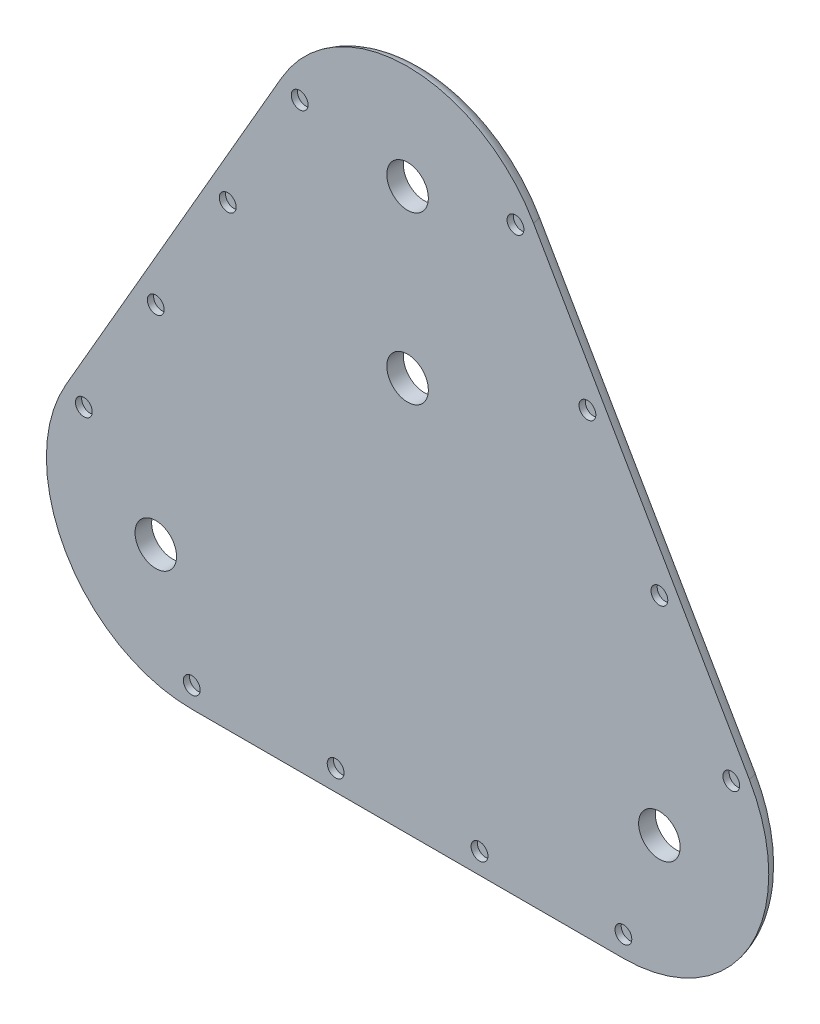
SolidWorks part; units mm, degrees
ref_plane "Plano frontal" through (0, 0, 0) normal (0, 0, 1) x (1, 0, 0)
ref_plane "Plano superior" through (0, 0, 0) normal (0, 1, 0) x (1, 0, 0)
ref_plane "Plano direito" through (0, 0, 0) normal (1, 0, 0) x (0, 0, -1)
sketch "Esboço1" plane through (0, 0, 0) normal (0, 0, 1) x (1, 0, 0)
  line L3 (-30.3109, 77.5) -> (-82.2724, -12.5)
  line L4 (-51.9615, -65) -> (51.9615, -65)
  line L5 (82.2724, -12.5) -> (30.3109, 77.5)
  arc A3 (-82.2724, -12.5) -> (-51.9615, -65) centre (-51.9615, -30) ccw
  arc A4 (51.9615, -65) -> (82.2724, -12.5) centre (51.9615, -30) ccw
  arc A5 (30.3109, 77.5) -> (-30.3109, 77.5) centre (0, 60) ccw
extrude "Ressalto-extrusão1" add sketch "Esboço1" along normal blind 4
sketch "Esboço2" plane through (0, 0, 0) normal (0, 0, 1) x (1, 0, 0)
  line L0 (0, 0) -> (0, 70) construction
  circle A3 centre (0, 70) radius 5
  circle A4 centre (60.6218, -35) radius 5
  circle A5 centre (-60.6218, -35) radius 5
  circle A6 centre (0, 30) radius 5
  point P13 (0, 0)
  dimension "D1" = 70
  dimension "D2" = 10
  dimension "D4" = 10
  dimension "D5" = 30
  dimension "D3" = 3
extrude "Corte-extrusão1" cut sketch "Esboço2" along normal up to surface (4 mm away) up to face at (0, 0, 4)
sketch "Esboço3" plane through (0, 0, 4) normal (0, 0, 1) x (1, 0, 0)
  line L0 (-25.9808, 75) -> (-77.9423, -15) construction
  line L1 (-51.9615, -60) -> (51.9615, -60) construction
  line L2 (77.9423, -15) -> (25.9808, 75) construction
  line L3 (-30.3109, 77.5) -> (-82.2724, -12.5)
  line L4 (-51.9615, -65) -> (51.9615, -65)
  line L5 (82.2724, -12.5) -> (30.3109, 77.5)
  line L6 (-30.3109, 77.5) -> (-82.2724, -12.5) construction
  line L7 (-51.9615, -65) -> (51.9615, -65) construction
  line L8 (82.2724, -12.5) -> (30.3109, 77.5) construction
  arc A0 (-77.9423, -15) -> (-51.9615, -60) centre (-51.9615, -30) ccw construction
  arc A1 (51.9615, -60) -> (77.9423, -15) centre (51.9615, -30) ccw construction
  arc A2 (25.9808, 75) -> (-25.9808, 75) centre (0, 60) ccw construction
  arc A3 (30.3109, 77.5) -> (-30.3109, 77.5) centre (0, 60) ccw
  arc A4 (-82.2724, -12.5) -> (-51.9615, -65) centre (-51.9615, -30) ccw
  arc A5 (51.9615, -65) -> (82.2724, -12.5) centre (51.9615, -30) ccw
  arc A6 (30.3109, 77.5) -> (-30.3109, 77.5) centre (0, 60) ccw construction
  arc A7 (-82.2724, -12.5) -> (-51.9615, -65) centre (-51.9615, -30) ccw construction
  arc A8 (51.9615, -65) -> (82.2724, -12.5) centre (51.9615, -30) ccw construction
  circle A9 centre (-77.9423, -15) radius 2.025
  circle A10 centre (-51.9615, -60) radius 2.025
  circle A11 centre (77.9423, -15) radius 2.025
  circle A12 centre (-60.6223, 14.9991) radius 2.025
  circle A13 centre (-43.3023, 44.9982) radius 2.025
  circle A14 centre (-25.9823, 74.9974) radius 2.025
  circle A15 centre (60.6223, 14.9991) radius 2.025
  circle A16 centre (43.3023, 44.9982) radius 2.025
  circle A17 centre (25.9823, 74.9974) radius 2.025
  circle A18 centre (-17.3215, -60) radius 2.025
  circle A19 centre (17.3185, -60) radius 2.025
  circle A20 centre (51.9585, -60) radius 2.025
  dimension "D3" = 4.05
  dimension "D1" = 0
  dimension "D2" = 5
  dimension "D4" = 4
  dimension "D5" = 4
  dimension "D6" = 4
extrude "Corte-extrusão2" cut sketch "Esboço3" against normal blind 1.5
fillet "Filete1" radius 5 6 edges at (-82.2724, -47.5, 0) (-56.2917, 32.5, 0) (0, 95, 0) (56.2917, 32.5, 0) (82.2724, -47.5, 0) (0, -65, 0)
